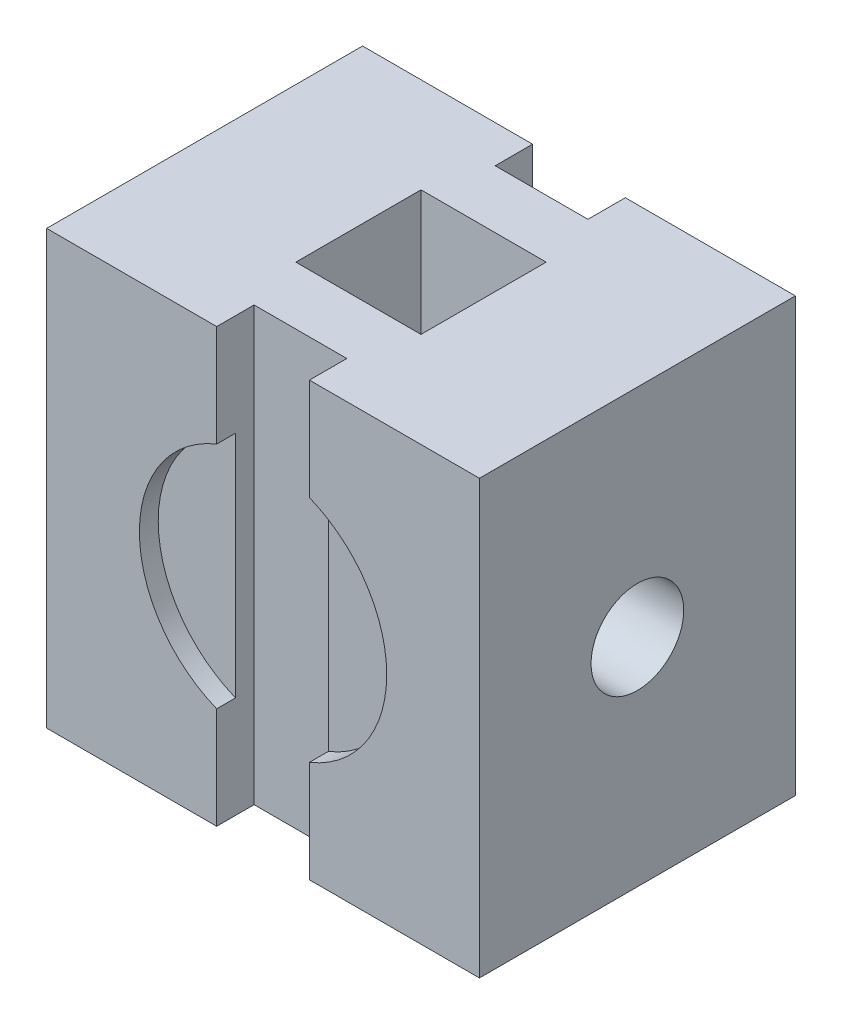
SolidWorks part; units mm, degrees
material "6061 Alloy"
ref_plane "Front Plane" through (0, 0, 0) normal (0, 0, 1) x (1, 0, 0)
ref_plane "Top Plane" through (0, 0, 0) normal (0, 1, 0) x (1, 0, 0)
ref_plane "Right Plane" through (0, 0, 0) normal (1, 0, 0) x (0, 0, -1)
ref_plane "Plane1" through (0, 0, 15) normal (0, 0, 1) x (1, 0, 0)
ref_plane "Plane2" through (0, 0, -15) normal (0, 0, 1) x (1, 0, 0)
sketch "Sketch2" plane through (0, 0, 15) normal (0, 0, 1) x (1, 0, 0)
  circle A0 centre (0, 0) radius 13.335
  dimension "D1" = 26.67
sketch "Sketch3" plane through (0, 0, -15) normal (0, 0, 1) x (1, 0, 0)
  circle A0 centre (0, 0) radius 13.335
  dimension "D1" = 26.67
extrude "Boss-Extrude1" add sketch "Sketch2" along normal blind 2.032 contours A0
extrude "Boss-Extrude2" add sketch "Sketch3" against normal blind 2.032 separate body contours A0
sketch "Sketch5" plane through (0, 0, 0) normal (0, 0, 1) x (1, 0, 0)
  line L0 (13.335, 0) -> (13.335, 23.335) construction
  line L1 (-23.335, -23.335) -> (23.335, -23.335)
  line L2 (-23.335, -23.335) -> (-23.335, 23.335)
  line L3 (-23.335, 23.335) -> (23.335, 23.335)
  line L4 (23.335, -23.335) -> (23.335, 23.335)
  line L5 (-23.335, -23.335) -> (23.335, 23.335) construction
  line L6 (-23.335, 23.335) -> (23.335, -23.335) construction
  line L7 (0, 13.335) -> (-23.335, 13.335) construction
  circle A0 centre (0, 0) radius 13.335 construction
  point P0 (0, 0)
  dimension "D1" = 10
  dimension "D2" = 10
extrude "Boss-Extrude3" add sketch "Sketch5" along normal up to surface (17.032 mm away) and the other way up to surface (17.032 mm away) separate body up to face at (13.335, 0, 17.032) other way up to face at (13.335, 0, -17.032)
sketch "Sketch6" plane through (-23.335, 0, 0) normal (-1, 0, 0) x (0, 0, 1)
  circle A0 centre (0, 0) radius 5
  dimension "D1" = 10
extrude "Cut-Extrude1" cut sketch "Sketch6" against normal through all
sketch "Sketch7" plane through (0, 23.335, 0) normal (0, 1, 0) x (1, 0, 0)
  line L1 (-6.75, -6.75) -> (6.75, -6.75)
  line L2 (-6.75, -6.75) -> (-6.75, 6.75)
  line L3 (-6.75, 6.75) -> (6.75, 6.75)
  line L4 (6.75, -6.75) -> (6.75, 6.75)
  line L5 (-6.75, -6.75) -> (6.75, 6.75) construction
  line L6 (-6.75, 6.75) -> (6.75, -6.75) construction
  point P0 (0, 0)
  dimension "D1" = 13.5
extrude "Cut-Extrude2" cut sketch "Sketch7" against normal offset from surface (31.67 mm away) 15 up to face at (0, -23.335, 0)
combine bodies "Combine1" operation type subtract main body 105 bodies to subtract 101 102
sketch "Sketch9" plane through (0, 0, 17.032) normal (0, 0, 1) x (1, 0, 0)
  line L6 (23.335, 23.335) -> (-23.335, 23.335) construction
  line L7 (-5, -23.335) -> (5, -23.335)
  line L8 (-5, -23.335) -> (-5, 23.335)
  line L9 (-5, 23.335) -> (5, 23.335)
  line L10 (5, -23.335) -> (5, 23.335)
  line L11 (-5, -23.335) -> (5, 23.335) construction
  line L12 (-5, 23.335) -> (5, -23.335) construction
  point P0 (0, 0)
  dimension "D1" = 10
extrude "Cut-Extrude3" cut sketch "Sketch9" against normal offset from surface (4.032 mm away) 2 contours L10 L9 L8 L7 up to face at (13.335, 0, 15) offset beyond the face yes
mirror "Mirror1" about plane through (0, 0, 0) normal (0, 0, 1) of "Cut-Extrude3"
